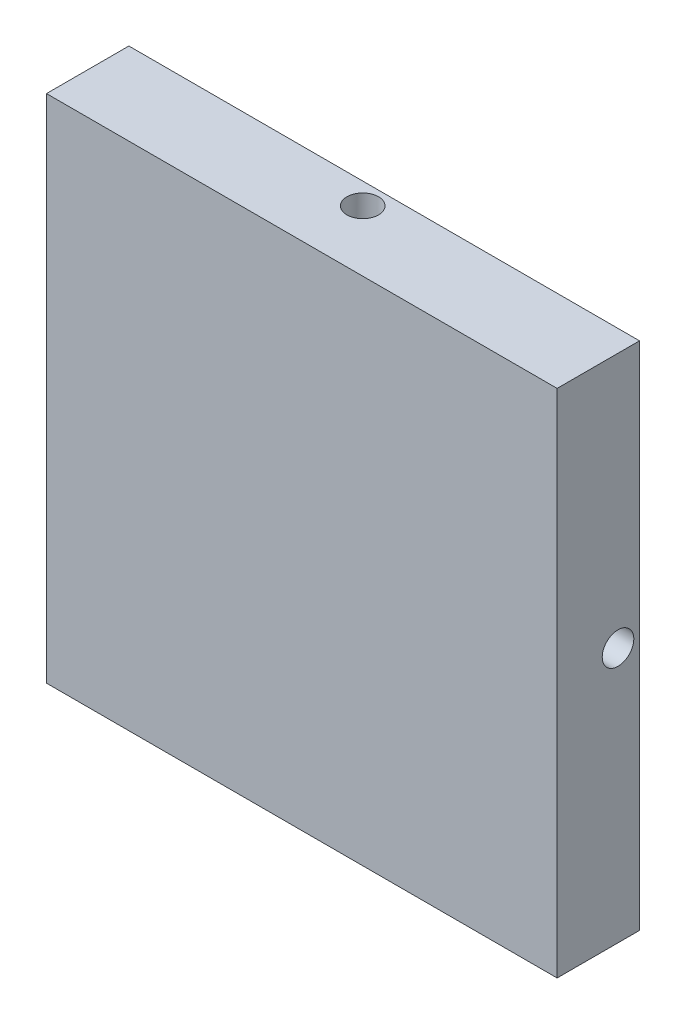
SolidWorks part; units mm, degrees
ref_plane "Front Plane" through (0, 0, 0) normal (0, 0, 1) x (1, 0, 0)
ref_plane "Top Plane" through (0, 0, 0) normal (0, 1, 0) x (1, 0, 0)
ref_plane "Right Plane" through (0, 0, 0) normal (1, 0, 0) x (0, 0, -1)
sketch "Sketch1" plane through (0, 0, 0) normal (0, 0, 1) x (1, 0, 0)
  line L0 (0, 0) -> (-12.9007, -35.4443) construction
  line L1 (-56.5785, 56.5785) -> (56.5785, 56.5785)
  line L2 (-56.5785, 56.5785) -> (-56.5785, -56.5785)
  line L3 (-56.5785, -56.5785) -> (56.5785, -56.5785)
  line L4 (56.5785, 56.5785) -> (56.5785, -56.5785)
  line L5 (0, 0) -> (0, -51.5938) construction
  line L6 (-27.4443, 51.5938) -> (31.5245, 51.5938) construction
  circle A0 centre (0, 0) radius 51.5938
  circle A1 centre (-12.9007, -35.4443) radius 3.175
  circle A2 centre (0, 0) radius 3.175
  circle A3 centre (-24.2453, 28.8944) radius 3.175
  circle A4 centre (37.146, 6.5498) radius 3.175
  circle A5 centre (-43.8785, 43.8785) radius 3.175
  circle A6 centre (43.8785, 43.8785) radius 3.175
  circle A7 centre (43.8785, -43.8785) radius 3.175
  circle A8 centre (-43.8785, -43.8785) radius 3.175
  point P12 (0, 56.5785)
  point P18 (0, 0)
  point P23 (-56.5785, 0)
  point P29 (0, 0)
  dimension "D1" = 103.1875
  dimension "D4" = 6.35
  dimension "D5" = 6.35
  dimension "D7" = 6.35
  dimension "D2" = 37.719
  dimension "D3" = 20
  dimension "D8" = 12.7
  dimension "D9" = 90
  dimension "D10" = 12.7
  dimension "D11" = 4
  dimension "D12" = 56.5785
  dimension "D13" = 4.9847
  dimension "D6" = 3
extrude "Boss-Extrude1" add sketch "Sketch1" along normal blind 8.7312 contours L4 L1 L2 L3 A8 A7 A6 A5 A0 | A6 | A5 | A8 | A7 | A1 | A3 | A4 | A0 A4 A3 A2 A1 | A2 region at (0, 54.9782, 0) region at (-50.1345, 0, 0) region at (-12.9007, -35.4443, 0) region at (0, 0, 0) region at (-24.2453, 28.8944, 0) region at (37.146, 6.5498, 0) region at (-43.8785, 43.8785, 0) region at (43.8785, 43.8785, 0) region at (43.8785, -43.8785, 0) region at (-43.8785, -43.8785, 0)
extrude "Boss-Extrude2" add sketch "Sketch1<3>" against normal blind 9.525 contours L4 L1 L2 L3 A8 A7 A6 A5 A0 | A4 | A1 | A2 | A3 region at (0, 54.9782, 0) region at (-12.9007, -35.4443, 0) region at (0, 0, 0) region at (-24.2453, 28.8944, 0) region at (37.146, 6.5498, 0)
sketch "Sketch1<3>" plane through (0, 0, 0) normal (0, 0, 1) x (1, 0, 0) same geometry as "Sketch1"
extrude "Boss-Extrude3" add sketch "Sketch1<4>" against normal blind 18.3515 contours A2 region at (0, 0, 0)
sketch "Sketch1<4>" plane through (0, 0, 0) normal (0, 0, 1) x (1, 0, 0) same geometry as "Sketch1"
sketch "Sketch2" plane through (0, 56.5785, 0) normal (0, 1, 0) x (1, 0, 0)
  line L0 (-56.5785, 9.525) -> (56.5785, 9.525) construction
  circle A0 centre (0, 4.7625) radius 3.5
  dimension "D1" = 7
  dimension "D2" = 4.7625
extrude "Cut-Extrude1" cut sketch "Sketch2" against normal up to next
pattern_circular "CirPattern1" count 4 over 360 about axis through (0, 0, -9.525) along (0, 0, 1) of "Cut-Extrude1"
sketch "Sketch4" plane through (0, 0, 0) normal (0, 0, -1) x (-1, 0, 0)
  line L0 (-46.8941, 0) -> (-25.0102, 0) construction
  line L1 (-46.8941, 1.27) -> (-25.0102, 1.27)
  line L2 (-46.8941, -1.27) -> (-25.0102, -1.27)
  arc A0 (-46.8941, 1.27) -> (-46.8941, -1.27) centre (-46.8941, 0) ccw
  arc A1 (-25.0102, -1.27) -> (-25.0102, 1.27) centre (-25.0102, 0) ccw
  point P2 (-35.9522, 0)
  point P7 (-36.2127, 0)
  point P8 (-39.5126, 0)
  point P9 (-46.8941, 0)
  point P11 (-25.0102, 0)
  dimension "D1" = 2.54
extrude "Cut-Extrude2" cut sketch "Sketch4" against normal blind 5.08
fillet "Fillet3" radius 1.905 4 edges at (35.9522, 1.27, 0) (23.7402, 0, 0) (35.9522, -1.27, 0) (48.1641, 0, 0)
